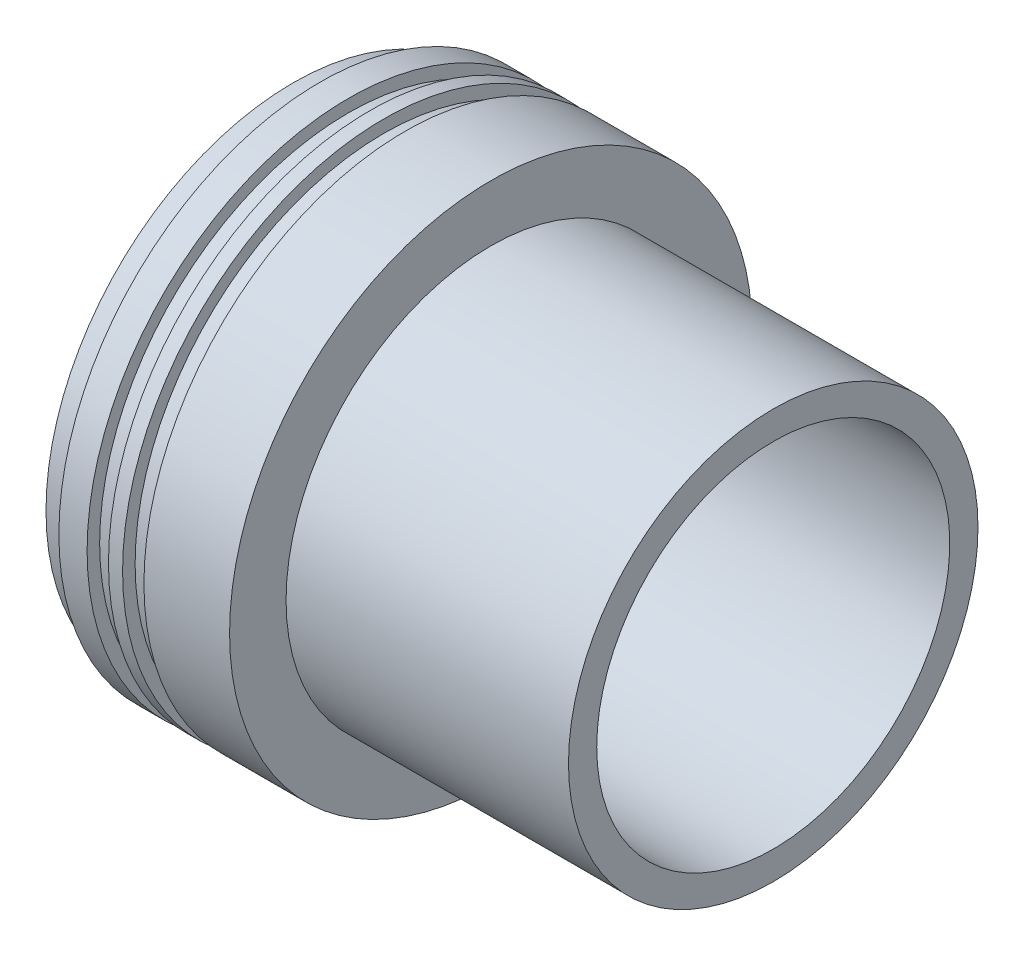
SolidWorks part; units mm, degrees
material "Epoxy, Unfilled"
ref_plane "Front Plane" through (0, 0, 0) normal (0, 0, 1) x (1, 0, 0)
ref_plane "Top Plane" through (0, 0, 0) normal (0, 1, 0) x (1, 0, 0)
ref_plane "Right Plane" through (0, 0, 0) normal (1, 0, 0) x (0, 0, -1)
sketch "Sketch1" plane through (0, 0, 0) normal (0, 0, 1) x (1, 0, 0)
  line L0 (0, 0) -> (0, 9.525)
  line L2 (0, 9.525) -> (22.7697, 9.525)
  line L4 (27.2599, 11.3849) -> (33.0651, 17.1901)
  line L5 (44.45, 0) -> (44.45, 12.7)
  line L6 (37.5553, 19.05) -> (107.95, 19.05)
  line L9 (44.45, 12.7) -> (107.95, 12.7)
  line L10 (107.95, 12.7) -> (107.95, 19.05)
  line L12 (0, 58.7375) -> (98.3752, 58.7375) construction
  line L17 (6.0659, 0) -> (12.4159, 0)
  line L18 (6.0659, 0) -> (6.0659, 3.175)
  line L19 (6.0659, 3.175) -> (0, 3.175)
  line L20 (12.4159, 0) -> (12.4159, 2.8194)
  line L21 (12.4159, 2.8194) -> (17.2165, 2.8194)
  line L22 (17.2165, 2.8194) -> (17.2165, 0)
  line L23 (17.2165, 0) -> (20.3915, 0)
  line L24 (20.3915, 0) -> (20.3915, 2.8194)
  line L25 (20.3915, 2.8194) -> (25.1921, 2.8194)
  line L26 (25.1921, 2.8194) -> (25.1921, 0)
  line L27 (25.1921, 0) -> (44.45, 0)
  arc A0 (27.2599, 11.3849) -> (22.7697, 9.525) centre (22.7697, 15.875) cw
  arc A1 (37.5553, 19.05) -> (33.0651, 17.1901) centre (37.5553, 12.7) ccw
  point P24 (25.4, 9.525)
  point P27 (34.925, 19.05)
  dimension "D15" = 6.35
  dimension "D16" = 6.35
  dimension "D1" = 63.5
  dimension "D2" = 25.4
  dimension "D3" = 58.7375
  dimension "D4" = 9.525
  dimension "D5" = 9.525
  dimension "D6" = 6.35
  dimension "D8" = 44.45
  dimension "D9" = 12.7
  dimension "D10" = 4.8006
  dimension "D11" = 4.8006
  dimension "D12" = 3.175
  dimension "D13" = 2.8194
  dimension "D14" = 2.8194
revolve "Revolve1" add sketch "Sketch1" angle 360 about L12 region at (1.0962, 6.35, 0)
